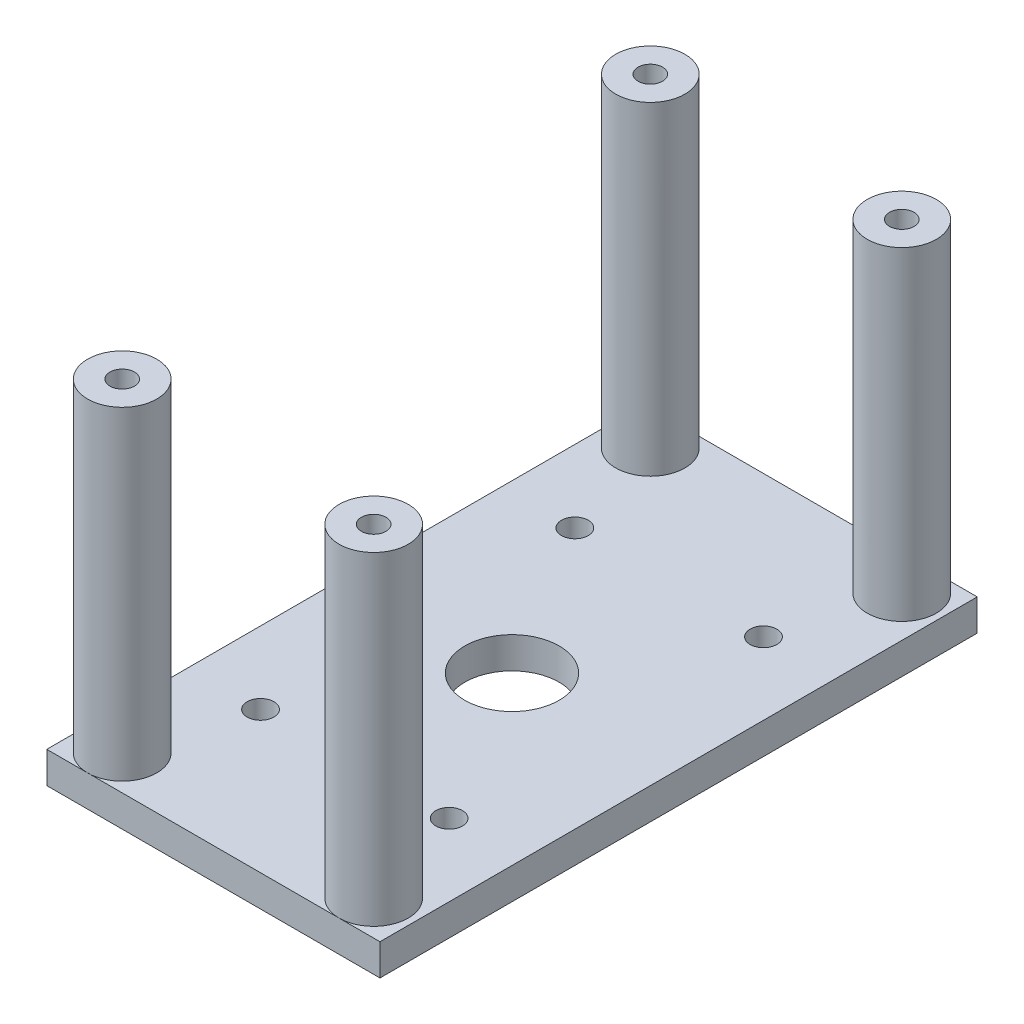
SolidWorks part; units mm, degrees
ref_plane "Front Plane" through (0, 0, 0) normal (0, 0, 1) x (1, 0, 0)
ref_plane "Top Plane" through (0, 0, 0) normal (0, 1, 0) x (1, 0, 0)
ref_plane "Right Plane" through (0, 0, 0) normal (1, 0, 0) x (0, 0, -1)
sketch "Sketch1" plane through (0, 0, 0) normal (0, 1, 0) x (1, 0, 0)
  line L1 (0, 0) -> (53, 0)
  line L2 (0, 0) -> (0, 95)
  line L3 (0, 95) -> (53, 95)
  line L4 (53, 0) -> (53, 95)
  dimension "D1" = 95
  dimension "D2" = 53
extrude "Boss-Extrude1" add sketch "Sketch1" along normal blind 5
sketch "Sketch2" plane through (0, 5, 0) normal (0, 1, 0) x (1, 0, 0)
  line L0 (53, 95) -> (0, 95) construction
  line L1 (0, 95) -> (0, 0) construction
  circle A0 centre (26.5, 47.5) radius 7.5 construction
  circle A1 centre (46.5, 89.5) radius 1.95
  circle A2 centre (6.5, 89.5) radius 1.95
  circle A3 centre (6.5, 5.5) radius 1.95
  circle A4 centre (46.5, 5.5) radius 1.95
  circle A5 centre (46.5, 89.5) radius 5.5
  circle A6 centre (6.5, 89.5) radius 5.5
  circle A7 centre (6.5, 5.5) radius 5.5
  circle A8 centre (46.5, 5.5) radius 5.5
  point P4 (26.5, 95)
  point P7 (0, 47.5)
  dimension "D1" = 15
  dimension "D2" = 42
  dimension "D5" = 3.9
  dimension "D6" = 40
  dimension "D7" = 11
  dimension "D3" = 20
  dimension "D4" = 84
extrude "Boss-Extrude2" add sketch "Sketch2" along normal blind 51.5
sketch "Sketch4" plane through (0, 5, 0) normal (0, 1, 0) x (1, 0, 0)
  line L1 (6.5, 0) -> (0, 0)
  circle A0 centre (26.5, 47.5) radius 7.5
  circle A1 centre (26.5, 47.5) radius 7.5 construction
  circle A2 centre (6.5, 5.5) radius 5.5 construction
  circle A4 centre (11.5, 72.5) radius 2.125
  circle A5 centre (41.5, 72.5) radius 2.125
  circle A6 centre (11.5, 22.5) radius 2.125
  circle A7 centre (41.5, 22.5) radius 2.125
  dimension "D1" = 4.25
  dimension "D2" = 30
  dimension "D3" = 15
  dimension "D4" = 50
  dimension "D5" = 25
extrude "Cut-Extrude1" cut sketch "Sketch4" against normal through all contours A0 | A4 | A5 | A6 | A7 region at (26.5, 5, -47.5)
